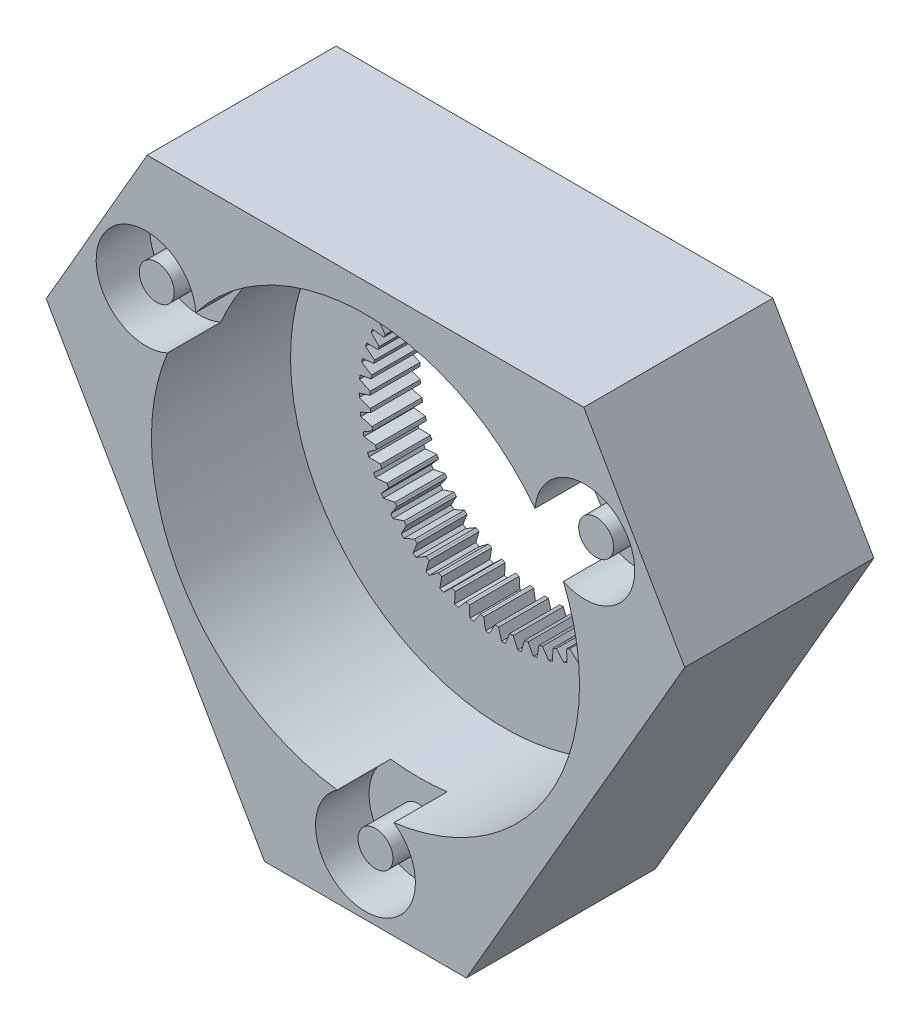
SolidWorks part; units mm, degrees
ref_plane "Front" through (0, 0, 0) normal (0, 0, 1) x (1, 0, 0)
ref_plane "Top" through (0, 0, 0) normal (0, 1, 0) x (1, 0, 0)
ref_plane "Right" through (0, 0, 0) normal (1, 0, 0) x (0, 0, -1)
sketch "Sketch1" plane through (0, 0, 0) normal (0, 0, 1) x (1, 0, 0)
  line L0 (0, 0) -> (0, -103) construction
  line L1 (39.2598, -68) -> (39.2598, -103)
  line L2 (-19.6299, -137) -> (19.6299, -137)
  line L3 (19.6299, -137) -> (39.2598, -103)
  line L4 (39.2598, -103) -> (19.6299, -69)
  line L5 (19.6299, -69) -> (-19.6299, -69)
  line L6 (-19.6299, -69) -> (-39.2598, -103)
  line L7 (-39.2598, -103) -> (-19.6299, -137)
  line L8 (39.2598, -68) -> (78.5196, 0)
  line L9 (78.5196, 0) -> (39.2598, 68)
  line L10 (39.2598, 68) -> (-39.2598, 68)
  line L11 (-39.2598, 68) -> (-78.5196, 0)
  line L12 (-78.5196, 0) -> (-39.2598, -68)
  line L13 (-39.2598, -68) -> (39.2598, -68)
  line L14 (-39.2598, -68) -> (-39.2598, -103)
  line L15 (-108.8305, 85.5) -> (-128.4604, 51.5)
  line L16 (-128.4604, 51.5) -> (-108.8305, 17.5)
  line L17 (-108.8305, 17.5) -> (-69.5707, 17.5)
  line L18 (-69.5707, 17.5) -> (-49.9408, 51.5)
  line L19 (-49.9408, 51.5) -> (-69.5707, 85.5)
  line L20 (-69.5707, 85.5) -> (-108.8305, 85.5)
  line L21 (-78.5196, 0) -> (-108.8305, 17.5)
  line L22 (-39.2598, 68) -> (-69.5707, 85.5)
  line L23 (128.4604, 51.5) -> (108.8305, 85.5)
  line L24 (108.8305, 85.5) -> (69.5707, 85.5)
  line L25 (69.5707, 85.5) -> (49.9408, 51.5)
  line L26 (49.9408, 51.5) -> (69.5707, 17.5)
  line L27 (69.5707, 17.5) -> (108.8305, 17.5)
  line L28 (108.8305, 17.5) -> (128.4604, 51.5)
  line L29 (39.2598, 68) -> (69.5707, 85.5)
  line L30 (78.5196, 0) -> (108.8305, 17.5)
  circle A0 centre (0, 0) radius 60
  circle A1 centre (0, 0) radius 68
  circle A2 centre (0, -103) radius 34 construction
  circle A3 centre (0, 0) radius 68 construction
  circle A4 centre (-89.2006, 51.5) radius 34 construction
  circle A5 centre (89.2006, 51.5) radius 34 construction
  point P42 (0, 0)
  dimension "D1" = 120
  dimension "D2" = 8
  dimension "D3" = 35
  dimension "D4" = 3
extrude "Boss-Extrude1" add sketch "Sketch1" along normal blind 10 contours L27 L28 L23 L24 L25 L26 | L9 L30 L27 L26 L25 L29 | A1 L9 L10 | A1 A0 | L19 L20 L15 L16 L17 L18 | L11 L22 L19 L18 L17 L21 | A1 L10 L11 | A1 L11 L12 | A1 L8 L9 | A1 L13 L8 | L13 L14 L6 L5 L4 L1 | L6 L7 L2 L3 L4 L5 | A1 L12 L13 region at (35.1411, -60.8662, 0) region at (38.4001, -85.5, 0) region at (0, -103, 0) region at (70.2823, 0, 0) region at (33.0383, -57.2241, 0) region at (-35.1411, -60.8662, 0) region at (68.8001, 17.0551, 0) region at (-70.2823, 0, 0) region at (35.1411, 60.8662, 0) region at (89.2006, 51.5, 0) region at (-93.1239, 9.7046, 0) region at (-35.1411, 60.8662, 0) region at (-89.2006, 51.5, 0)
sketch "Sketch2" plane through (0, 0, 10) normal (0, 0, 1) x (1, 0, 0)
  line L18 (-39.2598, -68) -> (-39.2598, -103)
  line L19 (-39.2598, -103) -> (-19.6299, -137)
  line L20 (-19.6299, -137) -> (19.6299, -137)
  line L21 (19.6299, -137) -> (39.2598, -103)
  line L22 (39.2598, -103) -> (39.2598, -68)
  line L23 (39.2598, -68) -> (78.5196, 0)
  line L24 (78.5196, 0) -> (108.8305, 17.5)
  line L25 (108.8305, 17.5) -> (128.4604, 51.5)
  line L26 (128.4604, 51.5) -> (108.8305, 85.5)
  line L27 (108.8305, 85.5) -> (69.5707, 85.5)
  line L28 (69.5707, 85.5) -> (39.2598, 68)
  line L29 (39.2598, 68) -> (-39.2598, 68)
  line L30 (-39.2598, 68) -> (-69.5707, 85.5)
  line L31 (-69.5707, 85.5) -> (-108.8305, 85.5)
  line L32 (-108.8305, 85.5) -> (-128.4604, 51.5)
  line L33 (-128.4604, 51.5) -> (-108.8305, 17.5)
  line L34 (-108.8305, 17.5) -> (-78.5196, 0)
  line L35 (-78.5196, 0) -> (-39.2598, -68)
  line L36 (-39.2598, -68) -> (-39.2598, -103)
  line L37 (-39.2598, -103) -> (-19.6299, -137)
  line L38 (-19.6299, -137) -> (19.6299, -137)
  line L39 (19.6299, -137) -> (39.2598, -103)
  line L40 (39.2598, -103) -> (39.2598, -68)
  line L41 (39.2598, -68) -> (78.5196, 0)
  line L42 (78.5196, 0) -> (108.8305, 17.5)
  line L43 (108.8305, 17.5) -> (128.4604, 51.5)
  line L44 (128.4604, 51.5) -> (108.8305, 85.5)
  line L45 (108.8305, 85.5) -> (69.5707, 85.5)
  line L46 (69.5707, 85.5) -> (39.2598, 68)
  line L47 (39.2598, 68) -> (-39.2598, 68)
  line L48 (-39.2598, 68) -> (-69.5707, 85.5)
  line L49 (-69.5707, 85.5) -> (-108.8305, 85.5)
  line L50 (-108.8305, 85.5) -> (-128.4604, 51.5)
  line L51 (-128.4604, 51.5) -> (-108.8305, 17.5)
  line L52 (-108.8305, 17.5) -> (-78.5196, 0)
  line L53 (-78.5196, 0) -> (-39.2598, -68)
  circle A0 centre (0, 0) radius 60 construction
  circle A1 centre (0, 0) radius 60
  circle A2 centre (0, 0) radius 68
  line M3 (-39.2598, -68) -> (-39.2598, -103)
  line M4 (-39.2598, -103) -> (-19.6299, -137)
  line M5 (-19.6299, -137) -> (19.6299, -137)
  line M6 (19.6299, -137) -> (39.2598, -103)
  line M7 (39.2598, -103) -> (39.2598, -68)
  line M8 (39.2598, -68) -> (78.5196, 0)
  line M9 (78.5196, 0) -> (108.8305, 17.5)
  line M10 (108.8305, 17.5) -> (128.4604, 51.5)
  line M11 (128.4604, 51.5) -> (108.8305, 85.5)
  line M12 (108.8305, 85.5) -> (69.5707, 85.5)
  line M13 (69.5707, 85.5) -> (39.2598, 68)
  line M14 (39.2598, 68) -> (-39.2598, 68)
  line M15 (-39.2598, 68) -> (-69.5707, 85.5)
  line M16 (-69.5707, 85.5) -> (-108.8305, 85.5)
  line M17 (-108.8305, 85.5) -> (-128.4604, 51.5)
  line M18 (-128.4604, 51.5) -> (-108.8305, 17.5)
  line M19 (-108.8305, 17.5) -> (-78.5196, 0)
  line M20 (-78.5196, 0) -> (-39.2598, -68)
  circle M21 centre (0, 0) radius 60
  dimension "D1" = 8
  dimension "D2" = 0
extrude "Boss-Extrude2" add sketch "Sketch2" along normal blind 50 contours A2 L41 M9 M10 M11 M12 M13 M14 | A2 M21 | A2 L53 M3 M4 M5 M6 M7 M8 | A2 L47 M15 M16 M17 M18 M19 M20 region at (0, -95.6096, 10) region at (-82.8003, 47.8048, 10) region at (-57.2241, 33.0383, 10) region at (82.8003, 47.8048, 10)
sketch "Sketch3" plane through (0, 0, 0) normal (0, 0, -1) x (-1, 0, 0)
  circle A0 centre (0, 0) radius 60 construction
  circle A1 centre (0, 0) radius 60
extrude "Boss-Extrude3" add sketch "Sketch3" against normal blind 6
chamfer "Chamfer1" distance 50 angle 45 3 edges at (0, -137, 60) (118.6455, 68.5, 60) (-118.6455, 68.5, 60)
chamfer "Chamfer4" [suppressed] distance 5.5 angle 45
sketch "Sketch4" [suppressed] plane through (0, 68, 0) normal (0, 1, 0) x (1, 0, 0)
  line L0 (0, -54.5) -> (0, 0) construction
  line L1 (-39.2598, -54.5) -> (39.2598, -54.5) construction
  line L2 (39.2598, 0) -> (-39.2598, 0) construction
  line L3 (0, -7.25) -> (11.25, -27.25)
  line L4 (0, -7.25) -> (-11.25, -27.25)
  line L5 (11.25, -27.25) -> (0, -47.25)
  line L6 (-11.25, -27.25) -> (0, -47.25)
  line L7 (11.25, -27.25) -> (-11.25, -27.25) construction
  line L8 (0, -10.3096) -> (-9.529, -27.25)
  line L9 (-9.529, -27.25) -> (0, -44.1904)
  line L10 (9.529, -27.25) -> (0, -44.1904)
  line L11 (0, -10.3096) -> (9.529, -27.25)
  line L12 (0, -20.5082) -> (-3.7922, -27.25)
  line L13 (-3.7922, -27.25) -> (0, -33.9918)
  line L14 (3.7922, -27.25) -> (0, -33.9918)
  line L15 (0, -20.5082) -> (3.7922, -27.25)
  line L16 (-2.0712, -27.25) -> (0, -30.9322)
  line L17 (2.0712, -27.25) -> (0, -30.9322)
  line L18 (0, -23.5678) -> (2.0712, -27.25)
  line L19 (0, -23.5678) -> (-2.0712, -27.25)
  point P11 (0, -27.25)
  dimension "D1" = 40
  dimension "D2" = 22.5
  dimension "D3" = 1.5
  dimension "D4" = 5
  dimension "D5" = 1.5
extrude "Boss-Extrude4" [suppressed] add sketch "Sketch4" along normal blind 1.5 contours L4 L6 L5 L3 L8 L11 L10 L9 | L15 L12 L13 L14 L19 L18 L17 L16
fillet "Fillet1" [suppressed] radius 0.7
sketch "Sketch5" plane through (0, 0, 0) normal (1, 0, 0) x (0, 0, -1)
  line L0 (0, 0) -> (-255.6292, 0) construction
pattern_circular "CirPattern1" [suppressed] count 3 over 240 about axis through (0, 0, 0) along (0, 0, 1) reverse direction yes of bodies 104
sketch "Sketch6" plane through (-63.6529, 36.75, 73.5) normal (-0.6124, 0.3536, 0.7071) x (0.7906, 0.2739, 0.5477)
  line L0 (-37.9967, 43.2241) -> (-41.3171, 39.1575)
  line L1 (-14.7885, 12.0748) -> (-69.5608, 56.7961) construction
  line L3 (-81.9758, 41.5909) -> (-57.1457, 72.0014) construction
  line L4 (-53.379, 43.5837) -> (-57.0226, 21.1654)
  line L5 (-57.0226, 21.1654) -> (-39.4296, 6.8008)
  line L7 (-39.4296, 6.8008) -> (-18.193, 14.8545)
  line L8 (-18.193, 14.8545) -> (-14.5493, 37.2728)
  line L9 (-14.5493, 37.2728) -> (-32.1423, 51.6374)
  line L10 (-32.1423, 51.6374) -> (-53.379, 43.5837)
  line L11 (10.0416, 42.4853) -> (-39.6186, -18.3358) construction
  line L12 (-169.1618, -435.9254) -> (75.74, -163.9344) construction
  line L16 (-21.6218, 29.854) -> (-33.5752, 15.2141) construction
  line L17 (-33.5752, 15.2141) -> (-49.9502, 28.5842) construction
  line L18 (-49.9502, 28.5842) -> (-37.9967, 43.2241) construction
  line L19 (-37.9967, 43.2241) -> (-21.6218, 29.854) construction
  line L20 (-21.6218, 29.854) -> (-27.5985, 22.5341) construction
  line L21 (-27.5985, 22.5341) -> (-43.9735, 35.9042) construction
  line L22 (-29.8093, 36.5391) -> (-41.7627, 21.8992) construction
  line L23 (-24.9422, 25.7874) -> (-31.1777, 30.8786)
  line L24 (-31.1777, 30.8786) -> (-36.4903, 24.372)
  line L25 (-21.6218, 29.854) -> (-24.9422, 25.7874)
  line L26 (-53.379, 43.5837) -> (-32.1423, 51.6374)
  line L27 (-30.2548, 19.2808) -> (-36.4903, 24.372)
  line L28 (-33.5752, 15.2141) -> (-30.2548, 19.2808)
  line L29 (-21.6218, 29.854) -> (-37.9967, 43.2241)
  line L30 (-33.5752, 15.2141) -> (-49.9502, 28.5842)
  line L31 (-49.9502, 28.5842) -> (-46.6298, 32.6509)
  line L32 (-46.6298, 32.6509) -> (-40.3943, 27.5596)
  line L33 (-35.0816, 34.0662) -> (-40.3943, 27.5596)
  line L34 (-41.3171, 39.1575) -> (-35.0816, 34.0662)
  circle A0 centre (-35.786, 29.2191) radius 19.6696 construction
  point P7 (-32.2205, 26.3079)
  point P21 (-3.551, 37.1803)
  point P34 (-33.834, 27.6253)
  dimension "D2" = 8.05
  dimension "D3" = 4.2
  dimension "D4" = 5.25
  dimension "D5" = 2.52
extrude "Boss-Extrude5" add sketch "Sketch6" along normal blind 2 contours L9 L10 L4 L5 L7 L8 L29 L25 L23 L24 L27 L28 L30 L31 L32 L33 L34 region at (-97.285, 67.1672, 29.1651)
chamfer "Chamfer5" distance 2 angle 45 6 edges at (-77.8201, 56.2857, 54.2913) (-87.6549, 39.2514, 54.2913) (-103.0037, 36.7567, 42.2462) (-108.5177, 51.2965, 30.2011) (-98.6829, 68.3308, 30.2011) (-83.3341, 70.8254, 42.2462)
pattern_circular "CirPattern2" count 3 over 240 about axis through (0, 0, 0) along (0, 0, 1) of "Boss-Extrude5", "Chamfer5"
sketch "Sketch7" plane through (0, 0, 6) normal (0, 0, 1) x (1, 0, 0)
  circle A0 centre (0, 0) radius 50
  circle A1 centre (0, 0) radius 60
  circle A2 centre (0, 0) radius 60
  dimension "D1" = 0
  dimension "D2" = 10
extrude "Boss-Extrude6" add sketch "Sketch7" along normal blind 15
sketch "Sketch8" plane through (0, 0, 60) normal (0, 0, 1) x (1, 0, 0)
  line L0 (-75.3442, 43.5) -> (-50.2295, 29) construction
  line L1 (-55.7143, 77.5) -> (-94.9741, 9.5) construction
  line L2 (-55.7143, 77.5) -> (-94.9741, 9.5) construction
  arc A0 (46.7938, -34.2686) -> (-32.372, 48.1254) centre (0, 0) ccw construction
  arc A1 (46.7938, -34.2686) -> (-32.372, 48.1254) centre (0, 0) ccw construction
  circle A2 centre (-61.4878, 35.5) radius 13
  circle A3 centre (-61.4878, 35.5) radius 14
  circle A4 centre (61.4878, 35.5) radius 14
  circle A5 centre (61.4878, 35.5) radius 13
  circle A6 centre (0, -71) radius 14
  circle A7 centre (0, -71) radius 13
  point P23 (0, 0)
  circle M21 centre (0, 0) radius 60
  dimension "D1" = 26
  dimension "D2" = 1
  dimension "D3" = 3
extrude "Cut-Extrude1" cut sketch "Sketch8" against normal blind 15 contours A2 M21 | A3 A2 M21 | A5 M21 | A5 A4 M21 | A7 M21 | A7 A6 M21 region at (-61.831, 35.6982, 60) region at (-73.1301, 42.1258, 60) region at (-7.1976, -59.9484, 60) region at (62.0301, 49.0935, 60) region at (0, -71.3963, 60) region at (61.831, 35.6982, 60)
sketch "Sketch9" plane through (0, 0, 45) normal (0, 0, 1) x (1, 0, 0)
  circle A0 centre (-61.4878, 35.5) radius 4.9
  circle A1 centre (61.6671, 35.1877) radius 4.9
  circle A2 centre (-0.1809, -71.3114) radius 4.9
  point P9 (-0.0005, -0.2079)
  dimension "D1" = 9.8
  dimension "D2" = 3
extrude "Boss-Extrude7" add sketch "Sketch9" along normal blind 12
sketch "Sketch10" [suppressed] plane through (0, 0, 0) normal (0, 0, -1) x (-1, 0, 0)
  line L0 (0, -137) -> (0, -62.9791) construction
  line L1 (18.4401, -137) -> (-18.4401, -137) construction
  line L2 (18.4401, -137) -> (-25.6702, -106.6531) construction
  line L3 (39.2598, -103) -> (21.0758, -134.4956) construction
  line L4 (-21.0758, -134.4956) -> (-39.2598, -103) construction
  circle A0 centre (0, -103) radius 34
  circle A1 centre (0, -103) radius 7.5
  circle A2 centre (-89.2006, 51.5) radius 7.5
  circle A3 centre (89.2006, 51.5) radius 7.5
  point P22 (0, 0)
  dimension "D1" = 15
  dimension "D2" = 3
extrude "Cut-Extrude2" [suppressed] cut sketch "Sketch10" against normal blind 15 contours A1 | A2 | A3
sketch "Sketch11" plane through (0, 0, 0) normal (0, 0, -1) x (-1, 0, 0)
  line L1 (49.7494, 5) -> (-49.7494, 5)
  line L2 (49.7494, 5) -> (49.7494, -5)
  line L3 (49.7494, -5) -> (-49.7494, -5)
  line L4 (-49.7494, 5) -> (-49.7494, -5)
  line L5 (49.7494, 5) -> (-49.7494, -5) construction
  line L6 (49.7494, -5) -> (-49.7494, 5) construction
  line L7 (-5, 49.7494) -> (5, 49.7494)
  line L8 (-5, 49.7494) -> (-5, -49.7494)
  line L9 (-5, -49.7494) -> (5, -49.7494)
  line L10 (5, 49.7494) -> (5, -49.7494)
  line L11 (-5, 49.7494) -> (5, -49.7494) construction
  line L12 (-5, -49.7494) -> (5, 49.7494) construction
  circle A1 centre (0, 0) radius 50
  circle A2 centre (0, 0) radius 50
  circle A3 centre (0, 0) radius 35
  circle A4 centre (0, 0) radius 15
  dimension "D3" = 30
  dimension "D4" = 10
  dimension "D5" = 10
  dimension "D1" = 0
  dimension "D2" = 15
extrude "Cut-Extrude3" cut sketch "Sketch11" against normal through all contours A4 L10 A3 L3 | A4 L1 A3 L10 | A4 L3 A3 L8 | A4 L8 A3 L1 | L1 A4 L10 | A4 L3 A3 L1 | L3 A4 L1 L10 | L10 A4 L3 | A4 L8 A3 L10 | L8 A4 L10 L3 | L10 L1 L8 L3 | L3 A4 L8 | L1 A4 L3 L8 | L8 A4 L1 | L10 A4 L8 L1 | A4 L10 A3 L8 | A4 L1 A3 L3 region at (-24.7977, 0, 0) region at (-17.8386, 17.8386, 0) region at (-9.862, 0, 0) region at (-8.5009, 8.5009, 0) region at (0, 24.7977, 0) region at (-17.8386, -17.8386, 0) region at (0, 0, 0) region at (0, 9.862, 0) region at (17.8386, 17.8386, 0) region at (-8.5009, -8.5009, 0) region at (0, -24.7977, 0) region at (9.862, 0, 0) region at (8.5009, 8.5009, 0) region at (0, -9.862, 0) region at (24.7977, 0, 0) region at (17.8386, -17.8386, 0) region at (8.5009, -8.5009, 0)
sketch "Sketch12" plane through (0, 0, 6) normal (0, 0, 1) x (1, 0, 0)
  line L0 (0, 0) -> (0, 42) construction
  line L1 (0, 39) -> (-0.5, 39)
  line L2 (-0.5, 39) -> (-1.5323, 41.972)
  line L3 (0, 0) -> (-4.4643, 41.7621) construction
  line L4 (-4.1454, 38.7791) -> (-3.6483, 38.8322)
  line L5 (-3.6483, 38.8322) -> (-2.5923, 41.9199)
  line L6 (-1.5323, 41.972) -> (-2.5923, 41.9199)
  line L7 (-2.5923, 41.9199) -> (-2.0623, 41.946) construction
  line L8 (0.5, 38.9981) -> (1.8892, 41.9509)
  line L9 (0, 39) -> (0.5, 38.9981)
  line L10 (3.6476, 38.8186) -> (2.9485, 41.8861)
  line L11 (4.1446, 38.7636) -> (3.6476, 38.8186)
  line L12 (2.9485, 41.8861) -> (1.8892, 41.9509)
  line L13 (4.6413, 38.7067) -> (6.347, 41.4888)
  line L14 (4.1446, 38.7636) -> (4.6413, 38.7067)
  line L15 (7.7501, 38.182) -> (7.3927, 41.3078)
  line L16 (8.238, 38.0726) -> (7.7501, 38.182)
  line L17 (7.3927, 41.3078) -> (6.347, 41.4888)
  line L18 (8.7255, 37.9615) -> (10.7268, 40.539)
  line L19 (8.238, 38.0726) -> (8.7255, 37.9615)
  line L20 (11.7577, 37.0979) -> (11.7463, 40.2441)
  line L21 (12.2306, 36.9356) -> (11.7577, 37.0979)
  line L22 (11.7463, 40.2441) -> (10.7268, 40.539)
  line L23 (12.7029, 36.7715) -> (14.9756, 39.1132)
  line L24 (12.2306, 36.9356) -> (12.7029, 36.7715)
  line L25 (15.6217, 35.5796) -> (15.9565, 38.708)
  line L26 (16.0738, 35.3662) -> (15.6217, 35.5796)
  line L27 (15.9565, 38.708) -> (14.9756, 39.1132)
  line L28 (16.5252, 35.1511) -> (19.0418, 37.2287)
  line L29 (16.0738, 35.3662) -> (16.5252, 35.1511)
  line L30 (19.2952, 33.6454) -> (19.9721, 36.718)
  line L31 (19.7211, 33.3836) -> (19.2952, 33.6454)
  line L32 (19.9721, 36.718) -> (19.0418, 37.2287)
  line L33 (20.1461, 33.1202) -> (22.8759, 34.9082)
  line L34 (19.7211, 33.3836) -> (20.1461, 33.1202)
  line L35 (22.7336, 31.3189) -> (23.7444, 34.2983)
  line L36 (23.1282, 31.0118) -> (22.7336, 31.3189)
  line L37 (23.7444, 34.2983) -> (22.8759, 34.9082)
  line L38 (23.5216, 30.7032) -> (26.4315, 32.1801)
  line L39 (23.1282, 31.0118) -> (23.5216, 30.7032)
  line L40 (25.8952, 28.6282) -> (27.2277, 31.4783)
  line L41 (26.2536, 28.2795) -> (25.8952, 28.6282)
  line L42 (27.2277, 31.4783) -> (26.4315, 32.1801)
  line L43 (26.6107, 27.9295) -> (29.6655, 29.0774)
  line L44 (26.2536, 28.2795) -> (26.6107, 27.9295)
  line L45 (28.7417, 25.606) -> (30.3796, 28.2923)
  line L46 (29.0595, 25.22) -> (28.7417, 25.606)
  line L47 (30.3796, 28.2923) -> (29.6655, 29.0774)
  line L48 (29.376, 24.8329) -> (32.5384, 25.6377)
  line L49 (29.0595, 25.22) -> (29.376, 24.8329)
  line L50 (31.2384, 22.289) -> (33.1618, 24.7788)
  line L51 (31.5118, 21.8704) -> (31.2384, 22.289)
  line L52 (33.1618, 24.7788) -> (32.5384, 25.6377)
  line L53 (31.7838, 21.4508) -> (35.0156, 21.9029)
  line L54 (31.5118, 21.8704) -> (31.7838, 21.4508)
  line L55 (33.355, 18.7175) -> (35.5407, 20.9806)
  line L56 (33.5808, 18.2714) -> (33.355, 18.7175)
  line L57 (35.5407, 20.9806) -> (35.0156, 21.9029)
  line L58 (33.8049, 17.8245) -> (37.0668, 17.9182)
  line L59 (33.5808, 18.2714) -> (33.8049, 17.8245)
  line L60 (35.0659, 14.9349) -> (37.4873, 16.9438)
  line L61 (35.2413, 14.4666) -> (35.0659, 14.9349)
  line L62 (37.4873, 16.9438) -> (37.0668, 17.9182)
  line L63 (35.4148, 13.9977) -> (38.6673, 13.7321)
  line L64 (35.2413, 14.4666) -> (35.4148, 13.9977)
  line L65 (36.3503, 10.987) -> (38.978, 12.7173)
  line L66 (36.4731, 10.5023) -> (36.3503, 10.987)
  line L67 (38.978, 12.7173) -> (38.6673, 13.7321)
  line L68 (36.594, 10.0171) -> (39.7975, 9.3953)
  line L69 (36.4731, 10.5023) -> (36.594, 10.0171)
  line L70 (37.1926, 6.9217) -> (39.9947, 8.3525)
  line L71 (37.2613, 6.4265) -> (37.1926, 6.9217)
  line L72 (39.9947, 8.3525) -> (39.7975, 9.3953)
  line L73 (37.3281, 5.931) -> (40.4438, 4.9605)
  line L74 (37.2613, 6.4265) -> (37.3281, 5.931)
  line L75 (37.5826, 2.7885) -> (40.5251, 3.9023)
  line L76 (37.5964, 2.2887) -> (37.5826, 2.7885)
  line L77 (40.5251, 3.9023) -> (40.4438, 4.9605)
  line L78 (37.6083, 1.7888) -> (40.5983, 0.4815)
  line L79 (37.5964, 2.2887) -> (37.6083, 1.7888)
  line L80 (37.5156, -1.3626) -> (40.5627, -0.5792)
  line L81 (37.4743, -1.8609) -> (37.5156, -1.3626)
  line L82 (40.5627, -0.5792) -> (40.5983, 0.4815)
  line L83 (37.4311, -2.359) -> (40.2591, -3.9873)
  line L84 (37.4743, -1.8609) -> (37.4311, -2.359)
  line L85 (36.9922, -5.481) -> (40.1071, -5.0376)
  line L86 (36.8964, -5.9718) -> (36.9922, -5.481)
  line L87 (40.1071, -5.0376) -> (40.2591, -3.9873)
  line L88 (36.7987, -6.4621) -> (39.4304, -8.3917)
  line L89 (36.8964, -5.9718) -> (36.7987, -6.4621)
  line L90 (36.019, -9.5169) -> (39.1637, -9.4189)
  line L91 (35.8698, -9.9942) -> (36.019, -9.5169)
  line L92 (39.1637, -9.4189) -> (39.4304, -8.3917)
  line L93 (35.7187, -10.4708) -> (38.1222, -12.6781)
  line L94 (35.8698, -9.9942) -> (35.7187, -10.4708)
  line L95 (34.6078, -13.4213) -> (37.7442, -13.6698)
  line L96 (34.4069, -13.8792) -> (34.6078, -13.4213)
  line L97 (37.7442, -13.6698) -> (38.1222, -12.6781)
  line L98 (34.2043, -14.3363) -> (36.3504, -16.7947)
  line L99 (34.4069, -13.8792) -> (34.2043, -14.3363)
  line L100 (32.7755, -17.1467) -> (35.8656, -17.7387)
  line L101 (32.5255, -17.5797) -> (32.7755, -17.1467)
  line L102 (35.8656, -17.7387) -> (36.3504, -16.7947)
  line L103 (32.2739, -18.0118) -> (34.1365, -20.6913)
  line L104 (32.5255, -17.5797) -> (32.2739, -18.0118)
  line L105 (30.5446, -20.6479) -> (33.5507, -21.5763)
  line L106 (30.2485, -21.0508) -> (30.5446, -20.6479)
  line L107 (33.5507, -21.5763) -> (34.1365, -20.6913)
  line L108 (29.9509, -21.4526) -> (31.5074, -24.3207)
  line L109 (30.2485, -21.0508) -> (29.9509, -21.4526)
  line L110 (27.942, -23.8825) -> (30.8278, -25.1359)
  line L111 (27.6034, -24.2504) -> (27.942, -23.8825)
  line L112 (30.8278, -25.1359) -> (31.5074, -24.3207)
  line L113 (27.2634, -24.617) -> (28.4949, -27.6389)
  line L114 (27.6034, -24.2504) -> (27.2634, -24.617)
  line L115 (24.9994, -26.8111) -> (27.7298, -28.3744)
  line L116 (24.6224, -27.1395) -> (24.9994, -26.8111)
  line L117 (27.7298, -28.3744) -> (28.4949, -27.6389)
  line L118 (24.2441, -27.4665) -> (25.1358, -30.6056)
  line L119 (24.6224, -27.1395) -> (24.2441, -27.4665)
  line L120 (21.7525, -29.3983) -> (24.2944, -31.2524)
  line L121 (21.3416, -29.6832) -> (21.7525, -29.3983)
  line L122 (24.2944, -31.2524) -> (25.1358, -30.6056)
  line L123 (20.9297, -29.9666) -> (21.4706, -33.1847)
  line L124 (21.3416, -29.6832) -> (20.9297, -29.9666)
  line L125 (18.2407, -31.6125) -> (20.5632, -33.735)
  line L126 (17.801, -31.8505) -> (18.2407, -31.6125)
  line L127 (20.5632, -33.735) -> (21.4706, -33.1847)
  line L128 (17.3604, -32.0868) -> (17.544, -35.345)
  line L129 (17.801, -31.8505) -> (17.3604, -32.0868)
  line L130 (14.5067, -33.427) -> (16.5815, -35.7921)
  line L131 (14.0434, -33.6152) -> (14.5067, -33.427)
  line L132 (16.5815, -35.7921) -> (17.544, -35.345)
  line L133 (13.5795, -33.8016) -> (13.4035, -37.0602)
  line L134 (14.0434, -33.6152) -> (13.5795, -33.8016)
  line L135 (10.5956, -34.8197) -> (12.3977, -37.3987)
  line L136 (10.1145, -34.9558) -> (10.5956, -34.8197)
  line L137 (12.3977, -37.3987) -> (13.4035, -37.0602)
  line L138 (9.6329, -35.09) -> (9.0995, -38.3094)
  line L139 (10.1145, -34.9558) -> (9.6329, -35.09)
  line L140 (6.5551, -35.7737) -> (8.0626, -38.5353)
  line L141 (6.062, -35.856) -> (6.5551, -35.7737)
  line L142 (8.0626, -38.5353) -> (9.0995, -38.3094)
  line L143 (5.5685, -35.9365) -> (4.6842, -39.0777)
  line L144 (6.062, -35.856) -> (5.5685, -35.9365)
  line L145 (2.4342, -36.2775) -> (3.6287, -39.1881)
  line L146 (1.935, -36.305) -> (2.4342, -36.2775)
  line L147 (3.6287, -39.1881) -> (4.6842, -39.0777)
  line L148 (1.4356, -36.3307) -> (0.2112, -39.3555)
  line L149 (1.935, -36.305) -> (1.4356, -36.3307)
  line L150 (-1.7171, -36.3248) -> (-0.8501, -39.3492)
  line L151 (-2.2163, -36.2973) -> (-1.7171, -36.3248)
  line L152 (-0.8501, -39.3492) -> (0.2112, -39.3555)
  line L153 (-2.7155, -36.2678) -> (-4.2652, -39.1396)
  line L154 (-2.2163, -36.2973) -> (-2.7155, -36.2678)
  line L155 (-5.8484, -35.9152) -> (-5.3194, -39.0166)
  line L156 (-6.3416, -35.8329) -> (-5.8484, -35.9152)
  line L157 (-5.3194, -39.0166) -> (-4.2652, -39.1396)
  line L158 (-6.8345, -35.7487) -> (-8.6908, -38.4326)
  line L159 (-6.3416, -35.8329) -> (-6.8345, -35.7487)
  line L160 (-9.9096, -35.0535) -> (-9.725, -38.1943)
  line L161 (-10.3908, -34.9175) -> (-9.9096, -35.0535)
  line L162 (-9.725, -38.1943) -> (-8.6908, -38.4326)
  line L163 (-10.8714, -34.7796) -> (-13.0117, -37.243)
  line L164 (-10.3908, -34.9175) -> (-10.8714, -34.7796)
  line L165 (-13.8514, -33.7504) -> (-14.0134, -36.8924)
  line L166 (-14.3146, -33.5622) -> (-13.8514, -33.7504)
  line L167 (-14.0134, -36.8924) -> (-13.0117, -37.243)
  line L168 (-14.7772, -33.3723) -> (-17.1755, -35.5853)
  line L169 (-14.3146, -33.5622) -> (-14.7772, -33.3723)
  line L170 (-17.6259, -32.0215) -> (-18.1325, -35.1266)
  line L171 (-18.0656, -31.7835) -> (-17.6259, -32.0215)
  line L172 (-18.1325, -35.1266) -> (-17.1755, -35.5853)
  line L173 (-18.5045, -31.5439) -> (-21.1316, -33.4796)
  line L174 (-18.0656, -31.7835) -> (-18.5045, -31.5439)
  line L175 (-21.1873, -29.8879) -> (-22.0324, -32.9185)
  line L176 (-21.5981, -29.603) -> (-21.1873, -29.8879)
  line L177 (-22.0324, -32.9185) -> (-21.1316, -33.4796)
  line L178 (-22.008, -29.3165) -> (-24.8321, -30.9515)
  line L179 (-21.5981, -29.603) -> (-22.008, -29.3165)
  line L180 (-24.4923, -27.3754) -> (-25.6657, -30.2946)
  line L181 (-24.8694, -27.0471) -> (-24.4923, -27.3754)
  line L182 (-25.6657, -30.2946) -> (-24.8321, -30.9515)
  line L183 (-25.2452, -26.7173) -> (-28.2321, -28.0316)
  line L184 (-24.8694, -27.0471) -> (-25.2452, -26.7173)
  line L185 (-27.5009, -24.5146) -> (-28.9883, -27.2871)
  line L186 (-27.8395, -24.1468) -> (-27.5009, -24.5146)
  line L187 (-28.9883, -27.2871) -> (-28.2321, -28.0316)
  line L188 (-28.1768, -23.7777) -> (-31.2901, -24.7555)
  line L189 (-27.8395, -24.1468) -> (-28.1768, -23.7777)
  line L190 (-30.1765, -21.3403) -> (-31.9599, -23.9322)
  line L191 (-30.4727, -20.9374) -> (-30.1765, -21.3403)
  line L192 (-31.9599, -23.9322) -> (-31.2901, -24.7555)
  line L193 (-30.7673, -20.5334) -> (-33.9693, -21.1628)
  line L194 (-30.4727, -20.9374) -> (-30.7673, -20.5334)
  line L195 (-32.4867, -17.8908) -> (-34.5444, -20.2709)
  line L196 (-32.7367, -17.4578) -> (-32.4867, -17.8908)
  line L197 (-34.5444, -20.2709) -> (-33.9693, -21.1628)
  line L198 (-32.9851, -17.0238) -> (-36.2369, -17.2972)
  line L199 (-32.7367, -17.4578) -> (-32.9851, -17.0238)
  line L200 (-34.4034, -14.2081) -> (-36.7104, -16.3474)
  line L201 (-34.6043, -13.7503) -> (-34.4034, -14.2081)
  line L202 (-36.7104, -16.3474) -> (-36.2369, -17.2972)
  line L203 (-34.8034, -13.2916) -> (-38.0655, -13.2056)
  line L204 (-34.6043, -13.7503) -> (-34.8034, -13.2916)
  line L205 (-35.9033, -10.337) -> (-38.4317, -12.2094)
  line L206 (-36.0526, -9.8598) -> (-35.9033, -10.337)
  line L207 (-38.4317, -12.2094) -> (-38.0655, -13.2056)
  line L208 (-36.2001, -9.382) -> (-39.433, -8.9376)
  line L209 (-36.0526, -9.8598) -> (-36.2001, -9.382)
  line L210 (-36.9683, -6.3243) -> (-39.6873, -7.9073)
  line L211 (-37.0642, -5.8336) -> (-36.9683, -6.3243)
  line L212 (-39.6873, -7.9073) -> (-39.433, -8.9376)
  line L213 (-37.1582, -5.3425) -> (-40.3226, -4.5451)
  line L214 (-37.0642, -5.8336) -> (-37.1582, -5.3425)
  line L215 (-37.5854, -2.2188) -> (-40.462, -3.4931)
  line L216 (-37.6267, -1.7205) -> (-37.5854, -2.2188)
  line L217 (-40.462, -3.4931) -> (-40.3226, -4.5451)
  line L218 (-37.6661, -1.2221) -> (-40.7236, -0.0815)
  line L219 (-37.6267, -1.7205) -> (-37.6661, -1.2221)
  line L220 (-37.7471, 1.9296) -> (-40.7465, 0.9796)
  line L221 (-37.7333, 2.4294) -> (-37.7471, 1.9296)
  line L222 (-40.7465, 0.9796) -> (-40.7236, -0.0815)
  line L223 (-37.7177, 2.9292) -> (-40.6311, 4.3992)
  line L224 (-37.7333, 2.4294) -> (-37.7177, 2.9292)
  line L225 (-37.4515, 6.0707) -> (-40.5371, 5.4563)
  line L226 (-37.3828, 6.5659) -> (-37.4515, 6.0707)
  line L227 (-40.5371, 5.4563) -> (-40.6311, 4.3992)
  line L228 (-37.3123, 7.0609) -> (-40.0463, 8.8425)
  line L229 (-37.3828, 6.5659) -> (-37.3123, 7.0609)
  line L230 (-36.7021, 10.1541) -> (-39.8366, 9.8829)
  line L231 (-36.5793, 10.6388) -> (-36.7021, 10.1541)
  line L232 (-39.8366, 9.8829) -> (-40.0463, 8.8425)
  line L233 (-36.4548, 11.123) -> (-38.9762, 13.1946)
  line L234 (-36.5793, 10.6388) -> (-36.4548, 11.123)
  line L235 (-35.508, 14.1302) -> (-38.6533, 14.2055)
  line L236 (-35.3327, 14.5985) -> (-35.508, 14.1302)
  line L237 (-38.6533, 14.2055) -> (-38.9762, 13.1946)
  line L238 (-35.1556, 15.0661) -> (-37.4338, 17.4025)
  line L239 (-35.3327, 14.5985) -> (-35.1556, 15.0661)
  line L240 (-33.8838, 17.9509) -> (-37.0017, 18.3718)
  line L241 (-33.658, 18.397) -> (-33.8838, 17.9509)
  line L242 (-37.0017, 18.3718) -> (-37.4338, 17.4025)
  line L243 (-33.4306, 18.8423) -> (-35.438, 21.4151)
  line L244 (-33.658, 18.397) -> (-33.4306, 18.8423)
  line L245 (-31.8491, 21.5697) -> (-34.9018, 22.331)
  line L246 (-31.5756, 21.9883) -> (-31.8491, 21.5697)
  line L247 (-34.9018, 22.331) -> (-35.438, 21.4151)
  line L248 (-31.3006, 22.4059) -> (-33.0128, 25.1839)
  line L249 (-31.5756, 21.9883) -> (-31.3006, 22.4059)
  line L250 (-29.4287, 24.9428) -> (-32.3791, 26.0353)
  line L251 (-29.1108, 25.3287) -> (-29.4287, 24.9428)
  line L252 (-32.3791, 26.0353) -> (-33.0128, 25.1839)
  line L253 (-28.7915, 25.7135) -> (-30.1877, 28.663)
  line L254 (-29.1108, 25.3287) -> (-28.7915, 25.7135)
  line L255 (-26.6519, 28.029) -> (-29.4642, 29.4395)
  line L256 (-26.2935, 28.3777) -> (-26.6519, 28.029)
  line L257 (-29.4642, 29.4395) -> (-30.1877, 28.663)
  line L258 (-25.9338, 28.725) -> (-26.997, 31.8102)
  line L259 (-26.2935, 28.3777) -> (-25.9338, 28.725)
  line L260 (-23.5524, 30.7911) -> (-26.1926, 32.5024)
  line L261 (-23.1579, 31.0982) -> (-23.5524, 30.7911)
  line L262 (-26.1926, 32.5024) -> (-26.997, 31.8102)
  line L263 (-22.7622, 31.4039) -> (-23.4795, 34.5873)
  line L264 (-23.1579, 31.0982) -> (-22.7622, 31.4039)
  line L265 (-20.1679, 33.1955) -> (-22.6038, 35.1868)
  line L266 (-19.742, 33.4573) -> (-20.1679, 33.1955)
  line L267 (-22.6038, 35.1868) -> (-23.4795, 34.5873)
  line L268 (-19.3151, 33.7176) -> (-19.6779, 36.9606)
  line L269 (-19.742, 33.4573) -> (-19.3151, 33.7176)
  line L270 (-16.5395, 35.2129) -> (-18.7415, 37.4601)
  line L271 (-16.0873, 35.4263) -> (-16.5395, 35.2129)
  line L272 (-18.7415, 37.4601) -> (-19.6779, 36.9606)
  line L273 (-15.6343, 35.638) -> (-15.6382, 38.9013)
  line L274 (-16.0873, 35.4263) -> (-15.6343, 35.638)
  line L275 (-12.7111, 36.8189) -> (-14.6525, 39.2948)
  line L276 (-12.2382, 36.9813) -> (-12.7111, 36.8189)
  line L277 (-14.6525, 39.2948) -> (-15.6382, 38.9013)
  line L278 (-11.7647, 37.1419) -> (-11.4095, 40.3858)
  line L279 (-12.2382, 36.9813) -> (-11.7647, 37.1419)
  line L280 (-8.7293, 37.9941) -> (-10.3866, 40.6684)
  line L281 (-8.2414, 38.1034) -> (-8.7293, 37.9941)
  line L282 (-10.3866, 40.6684) -> (-11.4095, 40.3858)
  line L283 (-7.7531, 38.2109) -> (-7.0433, 41.3961)
  line L284 (-8.2414, 38.1034) -> (-7.7531, 38.2109)
  line L285 (-4.6424, 38.7241) -> (-5.9954, 41.5645)
  line L286 (-4.1454, 38.7791) -> (-4.6424, 38.7241)
  line L287 (-5.9954, 41.5645) -> (-7.0433, 41.3961)
  circle A0 centre (0, 0) radius 50 construction
  circle A1 centre (0, 0) radius 42 construction
  circle A2 centre (0, 0) radius 50
  point P363 (-0.0704, 1.3208)
  dimension "D3" = 84
  dimension "D1" = 0.5
  dimension "D2" = 3
  dimension "D4" = 3
  dimension "D5" = 0.5
  dimension "D6" = 1.06
  dimension "D7" = 6.102
  dimension "D8" = 57
extrude "Boss-Extrude8" add sketch "Sketch12" along normal up to surface (15 mm away) up to face at (60, 0, 21)
sketch "Sketch13" plane through (0, 0, 60) normal (0, 0, 1) x (1, 0, 0)
  line L0 (39.2598, -68) -> (78.5196, 0) construction
  line L1 (39.2598, 68) -> (-39.2598, 68) construction
  line L2 (-78.5196, 0) -> (-39.2598, -68) construction
  line L3 (28.2902, -87) -> (89.4893, 19)
  line L4 (61.1991, 68) -> (-61.1991, 68)
  line L5 (-89.4893, 19) -> (-28.2902, -87)
  line L6 (108.8305, 17.5) -> (128.4604, 51.5)
  line L7 (128.4604, 51.5) -> (108.8305, 85.5)
  line L8 (108.8305, 85.5) -> (69.5707, 85.5)
  line L9 (69.5707, 85.5) -> (55.7143, 77.5)
  line L10 (55.7143, 77.5) -> (94.9741, 9.5)
  line L11 (94.9741, 9.5) -> (108.8305, 17.5)
  line L12 (108.8305, 17.5) -> (128.4604, 51.5)
  line L13 (128.4604, 51.5) -> (108.8305, 85.5)
  line L14 (108.8305, 85.5) -> (69.5707, 85.5)
  line L15 (69.5707, 85.5) -> (55.7143, 77.5)
  line L16 (55.7143, 77.5) -> (94.9741, 9.5)
  line L17 (94.9741, 9.5) -> (108.8305, 17.5)
  line L18 (-69.5707, 85.5) -> (-108.8305, 85.5)
  line L19 (-108.8305, 85.5) -> (-128.4604, 51.5)
  line L20 (-128.4604, 51.5) -> (-108.8305, 17.5)
  line L21 (-108.8305, 17.5) -> (-94.9741, 9.5)
  line L22 (-94.9741, 9.5) -> (-55.7143, 77.5)
  line L23 (-55.7143, 77.5) -> (-69.5707, 85.5)
  line L24 (-69.5707, 85.5) -> (-108.8305, 85.5)
  line L25 (-108.8305, 85.5) -> (-128.4604, 51.5)
  line L26 (-128.4604, 51.5) -> (-108.8305, 17.5)
  line L27 (-108.8305, 17.5) -> (-94.9741, 9.5)
  line L28 (-94.9741, 9.5) -> (-55.7143, 77.5)
  line L29 (-55.7143, 77.5) -> (-69.5707, 85.5)
  line L30 (-39.2598, -103) -> (-19.6299, -137)
  line L31 (-19.6299, -137) -> (19.6299, -137)
  line L32 (19.6299, -137) -> (39.2598, -103)
  line L33 (39.2598, -103) -> (39.2598, -87)
  line L34 (39.2598, -87) -> (-39.2598, -87)
  line L35 (-39.2598, -87) -> (-39.2598, -103)
  line L36 (-39.2598, -103) -> (-19.6299, -137)
  line L37 (-19.6299, -137) -> (19.6299, -137)
  line L38 (19.6299, -137) -> (39.2598, -103)
  line L39 (39.2598, -103) -> (39.2598, -87)
  line L40 (39.2598, -87) -> (-39.2598, -87)
  line L41 (-39.2598, -87) -> (-39.2598, -103)
  line M25 (-39.2598, -68) -> (-39.2598, -87)
  line M26 (-39.2598, -87) -> (39.2598, -87)
  line M27 (39.2598, -87) -> (39.2598, -68)
  line M29 (78.5196, 0) -> (94.9741, 9.5)
  line M30 (94.9741, 9.5) -> (55.7143, 77.5)
  line M31 (55.7143, 77.5) -> (39.2598, 68)
  line M33 (-39.2598, 68) -> (-55.7143, 77.5)
  line M34 (-55.7143, 77.5) -> (-94.9741, 9.5)
  line M35 (-94.9741, 9.5) -> (-78.5196, 0)
  dimension "D1" = 0
  dimension "D2" = 0
  dimension "D3" = 0
extrude "Cut-Extrude4" cut sketch "Sketch13" against normal through all both and the other way through all contours L17 L12 L13 L14 L15 M30 | L41 L36 L37 L38 L39 M26 | L3 M26 M27 | L5 M25 M26 | L5 M34 M35 | L29 L24 L25 L26 L27 M34 | L4 M33 M34 | L4 M30 M31 | L3 M29 M30 region at (35.6033, -80.6667, 60) region at (0, -109.2008, 60) region at (-35.6033, -80.6667, 60) region at (87.661, 9.5, 60) region at (94.5707, 54.6004, 60) region at (-87.661, 9.5, 60) region at (52.0577, 71.1667, 60) region at (-94.5707, 54.6004, 60) region at (-52.0577, 71.1667, 60)
sketch "Sketch14" plane through (0, 0, 0) normal (0, 0, -1) x (-1, 0, 0)
  line L6 (-89.4893, 19) -> (-28.2902, -87)
  line L7 (-28.2902, -87) -> (28.2902, -87)
  line L8 (28.2902, -87) -> (89.4893, 19)
  line L9 (89.4893, 19) -> (61.1991, 68)
  line L10 (61.1991, 68) -> (-61.1991, 68)
  line L11 (-61.1991, 68) -> (-89.4893, 19)
  line L12 (-89.4893, 19) -> (-28.2902, -87)
  line L13 (-28.2902, -87) -> (28.2902, -87)
  line L14 (28.2902, -87) -> (89.4893, 19)
  line L15 (89.4893, 19) -> (61.1991, 68)
  line L16 (61.1991, 68) -> (-61.1991, 68)
  line L17 (-61.1991, 68) -> (-89.4893, 19)
  dimension "D1" = 0
extrude "Cut-Extrude5" cut sketch "Sketch14" against normal blind 7
sketch "Sketch15" plane through (0, 0, 7) normal (0, 0, -1) x (-1, 0, 0)
  line L12 (-58.3124, 63) -> (-83.7158, 19)
  line L13 (-83.7158, 19) -> (-25.4034, -82)
  line L14 (-25.4034, -82) -> (25.4034, -82)
  line L15 (25.4034, -82) -> (83.7158, 19)
  line L16 (83.7158, 19) -> (58.3124, 63)
  line L17 (58.3124, 63) -> (-58.3124, 63)
  line L18 (-58.3124, 63) -> (-83.7158, 19)
  line L19 (-83.7158, 19) -> (-25.4034, -82)
  line L20 (-25.4034, -82) -> (25.4034, -82)
  line L21 (25.4034, -82) -> (83.7158, 19)
  line L22 (83.7158, 19) -> (58.3124, 63)
  line L23 (58.3124, 63) -> (-58.3124, 63)
  circle A0 centre (0, 0) radius 50
  dimension "D2" = 100
  dimension "D1" = 5
extrude "Cut-Extrude6" cut sketch "Sketch15" against normal blind 5
